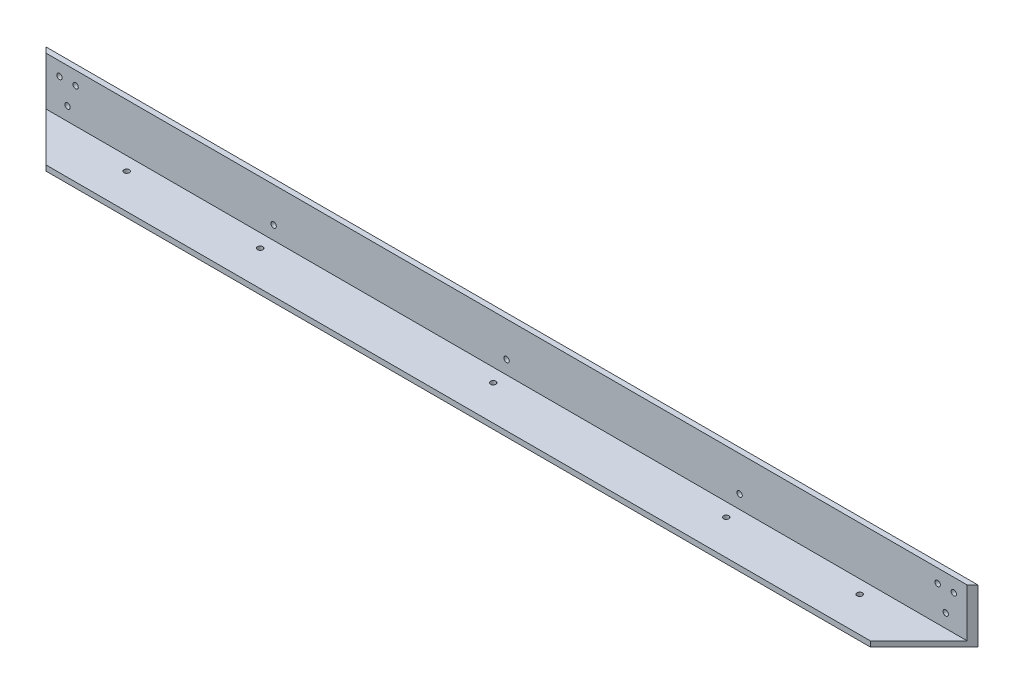
SolidWorks part; units mm, degrees
ref_plane "Front Plane" through (0, 0, 0) normal (0, 0, 1) x (1, 0, 0)
ref_plane "Top Plane" through (0, 0, 0) normal (0, 1, 0) x (1, 0, 0)
ref_plane "Right Plane" through (0, 0, 0) normal (1, 0, 0) x (0, 0, -1)
sketch "Sketch1" plane through (0, 0, 0) normal (1, 0, 0) x (0, 0, -1)
  line L0 (0, 0) -> (-31.75, 0)
  line L1 (-31.75, 0) -> (-31.75, 3.175)
  line L2 (-31.75, 3.175) -> (-3.175, 3.175)
  line L3 (-3.175, 3.175) -> (-3.175, 31.75)
  line L4 (-3.175, 31.75) -> (0, 31.75)
  line L5 (0, 31.75) -> (0, 0)
  dimension "LHeight" = 31.75
  dimension "LWidth" = 31.75
  dimension "LMaterialThickness" = 3.175
  dimension "D1" = 28.575
  dimension "D2" = 28.575
  dimension "D3" = 3.175
extrude "Boss-Extrude1" add sketch "Sketch1" along normal blind 550
chamfer "Chamfer6" distance 31.75 angle 45 1 edges at (550, 1.5875, 31.75)
chamfer "Chamfer7" distance 31.75 angle 45 1 edges at (0, 1.5875, 31.75)
sketch "TopHoles-Sketch3" plane through (0, 3.175, 0) normal (0, 1, 0) x (1, 0, 0)
  line L3 (550, 0) -> (0, 0) construction
  circle A9 centre (491.2625, -11.1125) radius 1.5875
  circle A10 centre (58.7375, -11.1125) radius 1.5875
  circle A13 centre (275, -11.1125) radius 1.5875
  circle A14 centre (137.5, -11.1125) radius 1.5875
  circle A15 centre (412.5, -11.1125) radius 1.5875
  dimension "D8" = 137.5
  dimension "D10" = 137.5
  dimension "D5" = 3.175
  dimension "D11" = 137.5
  dimension "D2" = 11.1125
  dimension "D3" = 58.7375
  dimension "D4" = 58.7375
extrude "TopHoles-Cut-Extrude2" cut sketch "TopHoles-Sketch3" against normal through all
sketch "LeftHoles-Sketch4" plane through (0, 0, 3.175) normal (0, 0, 1) x (1, 0, 0)
  line L1 (550, 0) -> (0, 0) construction
  line L3 (550, 31.75) -> (0, 31.75) construction
  line L4 (0, 0) -> (0, 31.75) construction
  line L5 (550, 0) -> (550, 31.75) construction
  circle A1 centre (11.1125, 23.8125) radius 1.5875
  circle A3 centre (529.3625, 23.8125) radius 1.5875
  circle A4 centre (20.6375, 23.8125) radius 1.5875
  circle A5 centre (538.8875, 23.8125) radius 1.5875
  circle A7 centre (15.875, 11.1125) radius 1.5875
  circle A8 centre (534.125, 11.1125) radius 1.5875
  circle A10 centre (137.5, 11.1125) radius 1.5875
  circle A11 centre (275, 11.1125) radius 1.5875
  circle A12 centre (412.5, 11.1125) radius 1.5875
  dimension "D2" = 3.175
  dimension "D4" = 7.9375
  dimension "D1" = 11.1125
  dimension "D6" = 20.6375
  dimension "D3" = 11.1125
  dimension "D5" = 20.6375
  dimension "D8" = 137.5
  dimension "D9" = 137.5
  dimension "D10" = 137.5
  dimension "D7" = 11.1125
  dimension "D11" = 15.875
  dimension "D12" = 15.875
extrude "LeftHoles-Cut-Extrude3" cut sketch "LeftHoles-Sketch4" against normal through all
equation "\"TopRailWidth\"= 1.25in"
equation "\"TopRailHeight\"= 1.25in"
equation "\"RailThickness\"= .125in'Spec"
equation "\"SideRailHoleY1FromEdge\"= \"HoleOffsetFromEdge\""
equation "\"SideRailHoleX1FromSide\"= \"HoleOffsetFromSide\""
equation "\"SideRailLength\"= 550mm"
equation "\"VSWidth\"= 1.25in'Spec"
equation "\"HoleOffsetFromEdge\"= \"RailThickness\" * 2.5"
equation "\"HoleOffsetFromSide\"= \"RailThickness\" * 3.5"
equation "\"SideRailHoleX2FromSide\"= \"VSWidth\" - \"HoleOffsetFromEdge\" - \"RailThickness\"'Equals 20.6375"
equation "\"FasteningHoleDiameter\"= .125in"
equation "\"SideRailHoleY2FromSide\"= \"HoleOffsetFromSide\""
equation "\"D2@LeftHoles-Sketch4\"=\"FasteningHoleDiameter\""
equation "\"LWidth@Sketch1\"=\"TopRailWidth\""
equation "\"LHeight@Sketch1\"=\"TopRailHeight\""
equation "\"LMaterialThickness@Sketch1\"=\"RailThickness\""
equation "\"D1@Boss-Extrude1\"=\"SideRailLength\""
equation "\"D4@LeftHoles-Sketch4\"=\"SideRailHoleY1FromEdge\""
equation "\"D1@Chamfer6\"=\"TopRailWidth\""
equation "\"D1@Chamfer7\"=\"TopRailWidth\""
equation "\"D1@LeftHoles-Sketch4\"=\"SideRailHoleX1FromSide\""
equation "\"D6@LeftHoles-Sketch4\"=\"SideRailHoleX2FromSide\""
equation "\"D5@LeftHoles-Sketch4\"=\"SideRailHoleX2FromSide\""
equation "\"TopHoleY1FromSide\"= \"HoleOffsetFromSide\""
equation "\"TopCBLength\"= \"TopRailWidth\" * 2'Equals 63.5"
equation "\"LeftOrRightEnclosureHoleOffsets\"= \"SideRailLength\" / 4"
equation "\"D8@TopHoles-Sketch3\"=\"LeftOrRightEnclosureHoleOffsets\""
equation "\"D10@TopHoles-Sketch3\"=\"LeftOrRightEnclosureHoleOffsets\""
equation "\"D11@TopHoles-Sketch3\"=\"LeftOrRightEnclosureHoleOffsets\""
equation "\"D8@LeftHoles-Sketch4\"=\"LeftOrRightEnclosureHoleOffsets\""
equation "\"D9@LeftHoles-Sketch4\"=\"LeftOrRightEnclosureHoleOffsets\""
equation "\"D10@LeftHoles-Sketch4\"=\"LeftOrRightEnclosureHoleOffsets\""
equation "\"D7@LeftHoles-Sketch4\"=\"SideRailHoleY2FromSide\""
equation "\"LeftOrRightCornerEnclosureOffset\"= \"RailThickness\" + \"TopCBLength\" - \"HoleOffsetFromEdge\"'Equals 58.7375"
equation "\"D2@TopHoles-Sketch3\"=\"TopHoleY1FromSide\""
equation "\"D3@TopHoles-Sketch3\"=\"LeftOrRightCornerEnclosureOffset\""
equation "\"D4@TopHoles-Sketch3\"=\"LeftOrRightCornerEnclosureOffset\""
equation "\"D5@TopHoles-Sketch3\"=\"FasteningHoleDiameter\""
equation "\"VSMidSideRailHoleXFromSideToCenter\"= \"RailThickness\" * 6"
equation "\"D11@LeftHoles-Sketch4\"=\"VSMidSideRailHoleXFromSideToCenter\" - \"RailThickness\""
equation "\"D12@LeftHoles-Sketch4\"=\"VSMidSideRailHoleXFromSideToCenter\" - \"RailThickness\""
